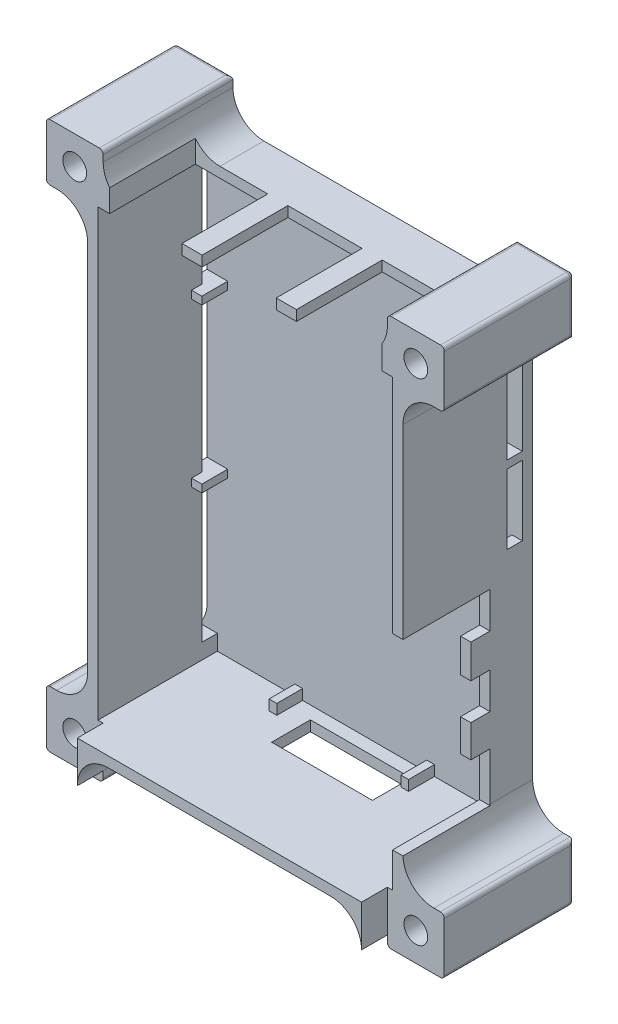
SolidWorks part; units mm, degrees
ref_plane "Front Plane" through (0, 0, 0) normal (0, 0, 1) x (1, 0, 0)
ref_plane "Top Plane" through (0, 0, 0) normal (0, 1, 0) x (1, 0, 0)
ref_plane "Right Plane" through (0, 0, 0) normal (1, 0, 0) x (0, 0, -1)
sketch "Sketch1" plane through (0, 0, 0) normal (0, 0, 1) x (1, 0, 0)
  line L1 (0, 0) -> (61, 0)
  line L2 (0, 0) -> (0, 90)
  line L3 (0, 90) -> (61, 90)
  line L4 (61, 0) -> (61, 90)
  dimension "D1" = 61
  dimension "D2" = 90
extrude "Boss-Extrude1" add sketch "Sketch1" along normal blind 2
sketch "Sketch2" plane through (0, 0, 2) normal (0, 0, 1) x (1, 0, 0)
  line L7 (0, -16.225) -> (0, 16.225) construction
  line L8 (0, 90) -> (0, 0)
  line L9 (2, 90) -> (2, 2)
  line L10 (2, 2) -> (59, 2)
  line L11 (59, 2) -> (59, 90)
  line L12 (2, 88) -> (2, 2)
  line L13 (2, 2) -> (59, 2)
  line L14 (59, 2) -> (59, 88)
  line L15 (0, 0) -> (61, 0)
  line L18 (61, 90) -> (61, 0)
  line L20 (2, 88) -> (59, 88)
  line L21 (0, 90) -> (61, 90)
  dimension "D1" = 2
extrude "Boss-Extrude2" add sketch "Sketch2" along normal blind 6.6
sketch "Sketch3" plane through (0, 0, 2) normal (0, 0, 1) x (1, 0, 0)
  line L0 (59, 2) -> (2, 2) construction
  line L1 (44, 2) -> (42.5, 2)
  line L2 (44, 2) -> (44, 4)
  line L3 (44, 4) -> (42.5, 4)
  line L4 (42.5, 2) -> (42.5, 4)
  line L5 (2, 2) -> (2, 88) construction
  line L6 (17, 2) -> (18.5, 2)
  line L7 (17, 2) -> (17, 4)
  line L8 (17, 4) -> (18.5, 4)
  line L9 (18.5, 2) -> (18.5, 4)
  line L10 (2, 32) -> (4, 32)
  line L11 (2, 32) -> (2, 33.5)
  line L12 (2, 33.5) -> (4, 33.5)
  line L13 (4, 32) -> (4, 33.5)
  line L14 (59, 88) -> (59, 2) construction
  line L15 (59, 32) -> (57, 32)
  line L16 (59, 32) -> (59, 33.5)
  line L17 (59, 33.5) -> (57, 33.5)
  line L18 (57, 32) -> (57, 33.5)
  line L19 (2, 2) -> (2, 88) construction
  line L20 (59, 63.5) -> (57, 63.5)
  line L21 (59, 63.5) -> (59, 65)
  line L22 (59, 65) -> (57, 65)
  line L23 (57, 63.5) -> (57, 65)
  line L24 (2, 63.5) -> (4, 63.5)
  line L25 (2, 63.5) -> (2, 65)
  line L26 (2, 65) -> (4, 65)
  line L27 (4, 63.5) -> (4, 65)
  line L28 (59, 2) -> (2, 2) construction
  dimension "D1" = 1.5
  dimension "D2" = 1.5
  dimension "D3" = 1.5
  dimension "D4" = 1.5
  dimension "D5" = 1.5
  dimension "D6" = 1.5
  dimension "D7" = 2
  dimension "D8" = 2
  dimension "D9" = 2
  dimension "D10" = 2
  dimension "D11" = 2
  dimension "D12" = 2
  dimension "D13" = 30
  dimension "D14" = 30
  dimension "D15" = 30
  dimension "D16" = 30
  dimension "D17" = 15
  dimension "D18" = 15
extrude "Boss-Extrude3" add sketch "Sketch3" along normal blind 5
sketch "Sketch4" plane through (0, 0, 8.6) normal (0, 0, 1) x (1, 0, 0)
  line L1 (61, 90) -> (0, 90)
  line L3 (59, 88) -> (2, 88)
  line L5 (61, 90) -> (61, 0)
  line L6 (0, 90) -> (0, 0)
  line L7 (0, 0) -> (61, 0)
  line L8 (2, 2) -> (59, 2)
  line L9 (2, 88) -> (2, 2)
  line L10 (59, 2) -> (59, 88)
  line L11 (59, 2) -> (59, 88) construction
extrude "Boss-Extrude4" add sketch "Sketch4" along normal blind 16.5
sketch "Sketch5" plane through (0, 90, 0) normal (0, 1, 0) x (1, 0, 0)
  line L1 (57, -8.5) -> (40.4, -8.5)
  line L3 (57, -22.25) -> (40.4, -22.25) construction
  line L4 (40.4, -8.5) -> (40.4, -22.25)
  line L5 (61, 0) -> (0, 0) construction
  line L6 (61, -25.1) -> (0, -25.1) construction
  line L7 (36.5, -25.1) -> (22.15, -25.1)
  line L8 (36.5, -25.1) -> (36.5, -8.5)
  line L9 (36.5, -8.5) -> (22.15, -8.5)
  line L10 (22.15, -25.1) -> (22.15, -8.5)
  line L11 (0, -25.1) -> (0, 0) construction
  line L12 (18.25, -25.1) -> (4.25, -25.1)
  line L13 (18.25, -25.1) -> (18.25, -8.5)
  line L14 (18.25, -8.5) -> (4.25, -8.5)
  line L15 (4.25, -25.1) -> (4.25, -8.5)
  line L17 (57, -25.1) -> (40.4, -25.1)
  line L19 (57, -22.25) -> (40.4, -22.25) construction
  line L20 (40.4, -25.1) -> (40.4, -22.25)
  line L21 (57, -8.5) -> (57, -25.1)
  line L22 (61, -25.1) -> (61, 0) construction
  point P21 (61, -12.55)
  dimension "D2" = 16.6
  dimension "D3" = 13.75
  dimension "D4" = 8.5
  dimension "D5" = 4.25
  dimension "D6" = 3.9
  dimension "D7" = 14
  dimension "D8" = 8.5
  dimension "D9" = 8.5
  dimension "D10" = 3.9
  dimension "D11" = 4
  dimension "D12" = 0
extrude "Cut-Extrude1" cut sketch "Sketch5" against normal blind 2
sketch "Sketch7" plane through (61, 0, 0) normal (1, 0, 0) x (0, 0, -1)
  line L0 (-11.95, 18.25) -> (-11.95, 24.5)
  line L8 (-11.95, 18.25) -> (-8.25, 18.25)
  line L9 (-8.25, 8.75) -> (-8.25, 18.25)
  line L10 (-11.95, 24.5) -> (-8.25, 24.5)
  line L12 (-11.95, 38) -> (-8.25, 38)
  line L14 (-11.95, 31.5) -> (-8.25, 31.5)
  line L18 (-25.1, 0) -> (-25.1, 90) construction
  line L19 (-25.1, 8.75) -> (-25.1, 45)
  line L21 (-11.95, 38) -> (-11.95, 31.5)
  line L22 (-8.25, 8.75) -> (-25.1, 8.75)
  line L23 (-25.1, 45) -> (-8.25, 45)
  line L24 (-25.1, 0) -> (0, 0) construction
  line L25 (-8.25, 24.5) -> (-8.25, 31.5)
  line L26 (-8.25, 38) -> (-8.25, 45)
  line L28 (0, 0) -> (0, 90) construction
  line L29 (0, 33.55) -> (0, -33.55) construction
  line L30 (-2, 85) -> (-5, 85)
  line L31 (-2, 85) -> (-2, 50)
  line L32 (-2, 50) -> (-5, 50)
  line L33 (-5, 85) -> (-5, 50)
  line L34 (-25.1, 90) -> (0, 90) construction
  point P0 (-8.25, 13.5)
  point P16 (-8.25, 41.5)
  point P18 (-10.1, 18.25)
  point P20 (-8.25, 28)
  dimension "D1" = 9.5
  dimension "D2" = 28
  dimension "D3" = 7
  dimension "D4" = 7
  dimension "D5" = 13.5
  dimension "D6" = 41.5
  dimension "D7" = 3.7
  dimension "D8" = 3.7
  dimension "D9" = 8.25
  dimension "D10" = 0
  dimension "D11" = 0
  dimension "D12" = 2
  dimension "D13" = 5
  dimension "D14" = 3
  dimension "D15" = 35
extrude "Cut-Extrude2" cut sketch "Sketch7" against normal blind 2
sketch "Sketch8" plane through (0, 0, 0) normal (0, -1, 0) x (-1, 0, 0)
  line L2 (-22.5, -12) -> (-22.5, -4.5)
  line L3 (-22.5, -4.5) -> (-42, -4.5)
  line L4 (-42, -12) -> (-42, -4.5)
  line L5 (0, 16.555) -> (0, -16.555) construction
  line L6 (-61, -25.1) -> (-61, 0) construction
  line L7 (-33.55, 0) -> (33.55, 0) construction
  line L8 (-22.5, -12) -> (-42, -12)
  dimension "D1" = 22.5
  dimension "D2" = 19
  dimension "D3" = 4.5
  dimension "D4" = 7.5
extrude "Cut-Extrude3" cut sketch "Sketch8" against normal blind 2
sketch "Sketch9" plane through (0, 0, 0) normal (-1, 0, 0) x (0, 0, 1)
  line L0 (0, -33.55) -> (0, 33.55) construction
  line L1 (5, 85) -> (2, 85)
  line L2 (5, 85) -> (5, 5)
  line L3 (5, 5) -> (2, 5)
  line L4 (2, 85) -> (2, 5)
  line L5 (25.1, 90) -> (0, 90) construction
  line L6 (16.555, 0) -> (-16.555, 0) construction
  dimension "D1" = 2
  dimension "D2" = 3
  dimension "D3" = 5
  dimension "D4" = 5
extrude "Cut-Extrude4" cut sketch "Sketch9" against normal blind 2
sketch "Sketch10" plane through (0, 0, 25.1) normal (0, 0, 1) x (1, 0, 0)
  line L0 (61, 0) -> (61, 8.75) construction
  line L1 (0, 0) -> (61, 0)
  line L2 (0, 0) -> (0, 2)
  line L3 (0, 2) -> (61, 2)
  line L4 (61, 0) -> (61, 2)
  dimension "D1" = 2
extrude "Boss-Extrude5" add sketch "Sketch10" along normal blind 5
sketch "Sketch12" plane through (2, 0, 0) normal (-1, 0, 0) x (0, 0, 1)
  line L0 (5, 63.5) -> (2, 63.5) construction
  line L1 (2, 65) -> (5, 65)
  line L2 (2, 65) -> (2, 63.5)
  line L3 (2, 63.5) -> (5, 63.5)
  line L4 (5, 65) -> (5, 63.5)
  line L5 (5, 32) -> (2, 32) construction
  line L6 (2, 33.5) -> (5, 33.5)
  line L7 (2, 33.5) -> (2, 32)
  line L8 (2, 32) -> (5, 32)
  line L9 (5, 33.5) -> (5, 32)
extrude "Boss-Extrude6" add sketch "Sketch12" along normal blind 2
sketch "Sketch13" plane through (59, 0, 0) normal (1, 0, 0) x (0, 0, -1)
  line L1 (-2, 63.5) -> (-5, 63.5)
  line L2 (-2, 63.5) -> (-2, 65)
  line L3 (-2, 65) -> (-5, 65)
  line L4 (-5, 63.5) -> (-5, 65)
extrude "Boss-Extrude7" add sketch "Sketch13" along normal blind 2
sketch "Sketch20" plane through (0, 0, 0) normal (0, 0, -1) x (-1, 0, 0)
  line L0 (-61, 90) -> (0, 90) construction
  line L1 (-3, 3) -> (8, 3)
  line L2 (-3, 3) -> (-3, -8)
  line L3 (-3, -8) -> (8, -8)
  line L4 (8, 3) -> (8, -8)
  line L5 (-3, 3) -> (8, -8) construction
  line L6 (-3, -8) -> (8, 3) construction
  line L7 (-58, 87) -> (-69, 87)
  line L8 (-58, 87) -> (-58, 98)
  line L9 (-58, 98) -> (-69, 98)
  line L10 (-69, 87) -> (-69, 98)
  line L11 (-58, 87) -> (-69, 98) construction
  line L12 (-58, 98) -> (-69, 87) construction
  line L13 (-61, 0) -> (-61, 90) construction
  line L14 (0, 0) -> (-61, 0) construction
  line L15 (0, 90) -> (0, 0) construction
  point P4 (2.5, -2.5)
  point P9 (-63.5, 92.5)
  dimension "D1" = 3
  dimension "D2" = 3
  dimension "D3" = 11
  dimension "D4" = 11
  dimension "D5" = 3
  dimension "D6" = 11
  dimension "D7" = 3
  dimension "D8" = 11
extrude "Boss-Extrude8" add sketch "Sketch20" against normal up to surface (25.1 mm away) up to face at (2.0833, 60, 25.1)
sketch "Sketch25" plane through (0, 0, 25.1) normal (0, 0, 1) x (1, 0, 0)
  line L1 (3, 3) -> (-8, 3)
  line L2 (3, 3) -> (3, -8)
  line L3 (3, -8) -> (-8, -8)
  line L4 (-8, 3) -> (-8, -8)
  line L5 (3, 3) -> (-8, -8) construction
  line L6 (3, -8) -> (-8, 3) construction
  line L7 (3, -8) -> (3.25, -8)
  line L8 (3, -8) -> (3, 3)
  line L9 (3, 3) -> (3.25, 3)
  line L10 (3.25, -8) -> (3.25, 3)
  line L11 (3, -8) -> (3.25, 3) construction
  line L12 (3, 3) -> (3.25, -8) construction
  point P4 (-2.5, -2.5)
  point P10 (3.125, -2.5)
  dimension "D1" = 0.25
extrude "Cut-Extrude11" cut sketch "Sketch25" along normal through all contours L2 L1 L4 L3 | L8 L7 L10 L9
sketch "Sketch26" plane through (0, 0, 25.1) normal (0, 0, 1) x (1, 0, 0)
  line L1 (3, 3) -> (2, 3)
  line L2 (3, 3) -> (3, 2)
  line L3 (3, 2) -> (2, 2)
  line L4 (2, 3) -> (2, 2)
  line L5 (3, 3) -> (2, 2) construction
  line L6 (3, 2) -> (2, 3) construction
  line L7 (58, 87) -> (59, 87)
  line L8 (58, 87) -> (58, 88)
  line L9 (58, 88) -> (59, 88)
  line L10 (59, 87) -> (59, 88)
  line L11 (58, 87) -> (59, 88) construction
  line L12 (58, 88) -> (59, 87) construction
  point P4 (2.5, 2.5)
  point P10 (58.5, 87.5)
  dimension "D1" = 1
  dimension "D2" = 1
  dimension "D3" = 1
  dimension "D4" = 1
extrude "Cut-Extrude12" cut sketch "Sketch26" against normal up to surface (23.1 mm away) up to face at (30.4, 40.25, 2)
sketch "Sketch27" plane through (0, 0, 25.1) normal (0, 0, 1) x (1, 0, 0)
  line L0 (63.5, 98) -> (63.5, 87) construction
  line L1 (58, 98) -> (69, 98) construction
  line L2 (69, 87) -> (61, 87) construction
  line L3 (69, 92.5) -> (58, 92.5) construction
  line L4 (69, 98) -> (69, 87) construction
  line L5 (58, 90) -> (58, 98) construction
  line L6 (-2.5, -8) -> (-2.5, 3) construction
  line L7 (3, -8) -> (-8, -8) construction
  line L8 (-8, 3) -> (0, 3) construction
  line L9 (-8, -2.5) -> (3, -2.5) construction
  line L10 (-8, -8) -> (-8, 3) construction
  line L11 (3, 0) -> (3, -8) construction
  circle A0 centre (-2.5, -2.5) radius 2.3
  circle A1 centre (63.5, 92.5) radius 2.3
  dimension "D1" = 4.6
  dimension "D2" = 4.6
extrude "Cut-Extrude13" cut sketch "Sketch27" against normal through all
sketch "Sketch31" plane through (0, 0, 0) normal (0, 0, -1) x (-1, 0, 0)
  line L0 (-69, 98) -> (-69, 87) construction
  line L1 (-61.225, 88.5596) -> (-58.95, 92.5)
  line L2 (-58.95, 92.5) -> (-61.225, 96.4404)
  line L3 (-61.225, 96.4404) -> (-65.775, 96.4404)
  line L4 (-65.775, 96.4404) -> (-68.05, 92.5)
  line L5 (-68.05, 92.5) -> (-65.775, 88.5596)
  line L6 (-65.775, 88.5596) -> (-61.225, 88.5596)
  line L7 (4.775, -6.4404) -> (7.05, -2.5)
  line L8 (7.05, -2.5) -> (4.775, 1.4404)
  line L9 (4.775, 1.4404) -> (0.225, 1.4404)
  line L10 (0.225, 1.4404) -> (-2.05, -2.5)
  line L11 (-2.05, -2.5) -> (0.225, -6.4404)
  line L12 (0.225, -6.4404) -> (4.775, -6.4404)
  line L13 (8, -8) -> (8, 3) construction
  circle A0 centre (-63.5, 92.5) radius 3.9404 construction
  circle A1 centre (2.5, -2.5) radius 3.9404 construction
  dimension "D1" = 9.1
  dimension "D2" = 9.1
  dimension "D3" = 30
  dimension "D4" = 30
extrude "Cut-Extrude17" cut sketch "Sketch31" against normal blind 6
fillet "Fillet3" radius 6 1 edges at (58, 90, 12.55) type face fillet first side face at (29.5687, 90, 15.7375) second side face at (58, 94, 12.55)
fillet "Fillet4" radius 6 1 edges at (61, 87, 12.55) type face fillet first side face at (61, 75, 3.5) second side face at (65, 87, 12.55)
sketch "Sketch33" plane through (0, 0, 25.1) normal (0, 0, 1) x (1, 0, 0)
  line L0 (2, 2) -> (3.25, 2) construction
  line L1 (3.25, 0) -> (3, 0)
  line L2 (3.25, 0) -> (3.25, 2)
  line L3 (3.25, 2) -> (3, 2)
  line L4 (3, 0) -> (3, 2)
  line L5 (3.25, 0) -> (3, 2) construction
  line L6 (3.25, 2) -> (3, 0) construction
  point P4 (3.125, 1)
  dimension "D1" = 0.25
extrude "Boss-Extrude10" add sketch "Sketch33" along normal up to surface (5 mm away) up to face at (32.125, 1, 30.1)
fillet "Fillet7" radius 6 1 edges at (3, 0, 12.55) type face fillet first side face at (3, -4, 12.55) second side face at (32.25, 0, 8.25)
fillet "Fillet8" radius 6 1 edges at (0, 3, 12.55) type face fillet first side face at (-4, 3, 12.55) second side face at (0, 48.5, 3.5)
sketch "Sketch34" plane through (0, 0, 25.1) normal (0, 0, 1) x (1, 0, 0)
  line L0 (18.25, 90) -> (4.25, 90) construction
  line L1 (59, 3) -> (69, 3)
  line L2 (58, 2) -> (58, -8)
  line L3 (58, -8) -> (69, -8)
  line L4 (69, 3) -> (69, -8)
  line L5 (59, 2) -> (69, -8) construction
  line L6 (58, -8) -> (69, 3) construction
  line L7 (2, 87) -> (-8, 87)
  line L8 (3, 88) -> (3, 98)
  line L9 (3, 98) -> (-8, 98)
  line L10 (-8, 87) -> (-8, 98)
  line L11 (2, 88) -> (-8, 98) construction
  line L12 (3, 98) -> (-8, 87) construction
  line L13 (0, 90) -> (0, 9) construction
  line L14 (61, 0) -> (61, 2) construction
  line L15 (9, 0) -> (61, 0) construction
  line L16 (59, 88) -> (2, 88) construction
  line L17 (2, 88) -> (2, 2) construction
  line L18 (3, 88) -> (2, 88)
  line L19 (2, 88) -> (2, 87)
  line L20 (59, 2) -> (59, 8.75) construction
  line L21 (44, 2) -> (59, 2) construction
  line L22 (59, 2) -> (59, 3)
  line L23 (58, 2) -> (59, 2)
  point P4 (63.5, -2.5)
  point P9 (-2.5, 92.5)
  dimension "D1" = 3
  dimension "D2" = 3
  dimension "D3" = 3
  dimension "D4" = 3
  dimension "D5" = 11
  dimension "D6" = 11
  dimension "D7" = 11
  dimension "D8" = 11
extrude "Boss-Extrude11" add sketch "Sketch34" against normal up to surface (25.1 mm away) up to face at (30.5, 45, 0)
sketch "Sketch35" plane through (0, 0, 25.1) normal (0, 0, 1) x (1, 0, 0)
  line L0 (-2.5, 98) -> (-2.5, 87) construction
  line L1 (3, 98) -> (-8, 98) construction
  line L2 (-8, 87) -> (0, 87) construction
  line L3 (-8, 92.5) -> (3, 92.5) construction
  line L4 (-8, 98) -> (-8, 87) construction
  line L5 (3, 90) -> (3, 98) construction
  line L6 (63.5, -8) -> (63.5, 3) construction
  line L7 (58, -8) -> (69, -8) construction
  line L8 (69, 3) -> (61, 3) construction
  line L9 (69, -2.5) -> (58, -2.5) construction
  line L10 (69, -8) -> (69, 3) construction
  line L11 (58, 0) -> (58, -8) construction
  circle A0 centre (-2.5, 92.5) radius 2.3
  circle A1 centre (63.5, -2.5) radius 2.3
  dimension "D1" = 4.6
  dimension "D2" = 4.6
extrude "Cut-Extrude18" cut sketch "Sketch35" against normal through all
fillet "Fillet9" radius 6 1 edges at (0, 87, 12.55) type face fillet first side face at (-4, 87, 12.55) second side face at (0, 48.5, 3.5)
fillet "Fillet10" radius 6 1 edges at (3, 90, 12.55) type face fillet first side face at (3, 94, 12.55) second side face at (25.2214, 90, 14.4)
fillet "Fillet11" radius 6 1 edges at (61, 3, 12.55) type face fillet first side face at (65, 3, 12.55) second side face at (61, 39.6, 10.585)
fillet "Fillet13" radius 0.75 20 edges at (69, -2.5, 0) (63.5, -8, 0) (-2.5, -8, 0) (-8, -2.5, 0) (-8, 92.5, 0) (-2.5, 98, 0) (69, 92.5, 0) (63.5, 98, 0) (69, 87, 12.55) (69, 98, 12.55) (58, 98, 12.55) (3, 98, 12.55) (-8, 98, 12.55) (-8, 87, 12.55) (-8, 3, 12.55) (-8, -8, 12.55) (3, -8, 12.55) (69, 3, 12.55) (58, -8, 12.55) (69, -8, 12.55)
sketch "Sketch36" plane through (0, 0, 0) normal (0, 0, -1) x (-1, 0, 0)
  line L0 (8, 97.25) -> (8, 87.75) construction
  line L1 (-58.95, -2.5) -> (-61.225, 1.4404)
  line L2 (-61.225, 1.4404) -> (-65.775, 1.4404)
  line L3 (-65.775, 1.4404) -> (-68.05, -2.5)
  line L4 (-68.05, -2.5) -> (-65.775, -6.4404)
  line L5 (-65.775, -6.4404) -> (-61.225, -6.4404)
  line L6 (-61.225, -6.4404) -> (-58.95, -2.5)
  line L7 (-2.05, 92.5) -> (0.225, 88.5596)
  line L8 (0.225, 88.5596) -> (4.775, 88.5596)
  line L9 (4.775, 88.5596) -> (7.05, 92.5)
  line L10 (7.05, 92.5) -> (4.775, 96.4404)
  line L11 (4.775, 96.4404) -> (0.225, 96.4404)
  line L12 (0.225, 96.4404) -> (-2.05, 92.5)
  line L13 (-69, -7.25) -> (-69, 2.25) construction
  circle A0 centre (-63.5, -2.5) radius 3.9404 construction
  circle A1 centre (2.5, 92.5) radius 3.9404 construction
  dimension "D1" = 30
  dimension "D2" = 30
  dimension "D3" = 9.1
  dimension "D4" = 9.1
extrude "Cut-Extrude19" cut sketch "Sketch36" against normal blind 6
sketch "Sketch38" plane through (0, 0, 25.1) normal (0, 0, 1) x (1, 0, 0)
  line L1 (69, -8) -> (58, -8)
  line L2 (69, -8) -> (69, 3)
  line L3 (69, 3) -> (58, 3)
  line L4 (58, -8) -> (58, 3)
  line L6 (61, 0) -> (61, 2) construction
  dimension "D1" = 11
  dimension "D2" = 8
extrude "Cut-Extrude20" cut sketch "Sketch38" along normal blind 10
fillet "Fillet14" radius 6 1 edges at (58, 0, 12.55) type face fillet first side face at (32.25, 0, 8.25) second side face at (58, -3.625, 12.55)
